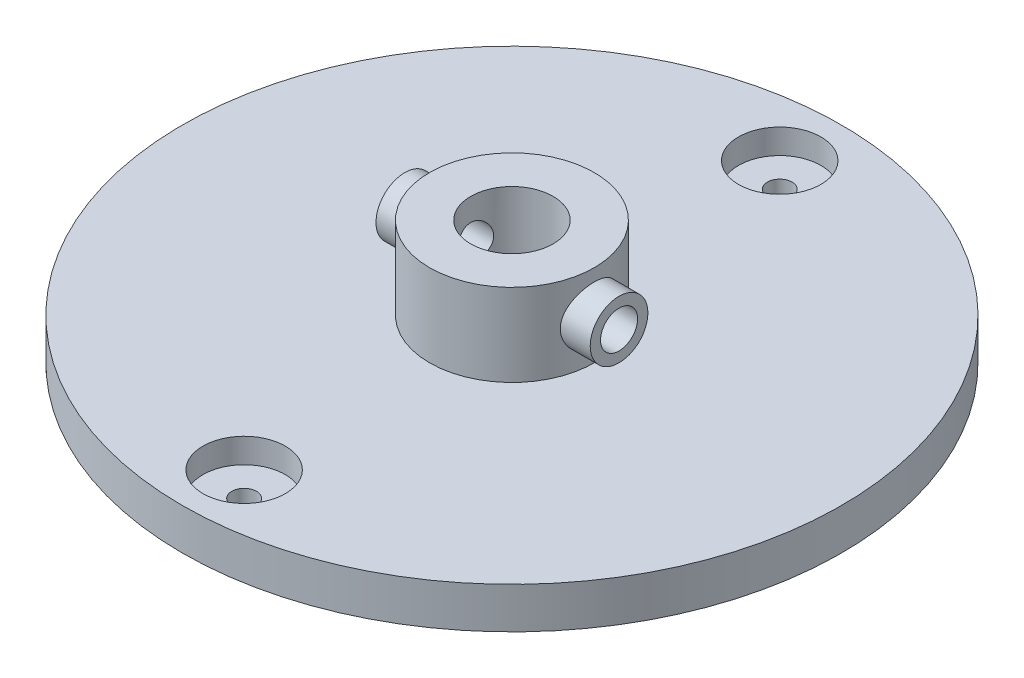
SolidWorks part; units mm, degrees
ref_plane "Front Plane" through (0, 0, 0) normal (0, 0, 1) x (1, 0, 0)
ref_plane "Top Plane" through (0, 0, 0) normal (0, 1, 0) x (1, 0, 0)
ref_plane "Right Plane" through (0, 0, 0) normal (1, 0, 0) x (0, 0, -1)
sketch "Sketch1" plane through (0, 0, 0) normal (0, 1, 0) x (1, 0, 0)
  circle A0 centre (4.1476, -5.4608) radius 40
  dimension "D1" = 80
extrude "Boss-Extrude1" add sketch "Sketch1" along normal blind 5
sketch "Sketch2" plane through (0, 5, 0) normal (0, 1, 0) x (1, 0, 0)
  line L0 (4.1476, -5.4608) -> (44.0651, -2.8922) construction
  line L1 (4.1476, -5.4608) -> (1.5791, 34.4567) construction
  circle A0 centre (4.1476, -5.4608) radius 5
  circle A1 centre (4.1476, -5.4608) radius 40 construction
  dimension "D2" = 10
  dimension "D1" = 40
extrude "Cut-Extrude1" cut sketch "Sketch2" against normal blind 15 contours A0
sketch "Sketch3" plane through (0, 5, 0) normal (0, 1, 0) x (1, 0, 0)
  line L0 (4.1476, -5.4608) -> (4.1476, 13.0674) construction
  line L1 (4.1476, -5.4608) -> (4.1476, -33.9971) construction
  line L2 (4.1476, -5.4608) -> (4.1476, 16.037) construction
  line L3 (4.1476, -5.4608) -> (4.1476, -35.1851) construction
  circle A0 centre (4.1476, -5.4608) radius 32.5 construction
  circle A1 centre (4.1476, 27.0392) radius 5
  circle A3 centre (4.1476, -37.9608) radius 5
  dimension "D1" = 65
  dimension "D3" = 10
  dimension "D2" = 0
extrude "Cut-Extrude2" cut sketch "Sketch3" against normal blind 3
sketch "Sketch5" plane through (0, 2, 0) normal (0, 1, 0) x (1, 0, 0)
  line L0 (4.1476, 27.0392) -> (-12.1024, -33.6066) construction
  line L1 (20.3976, 22.6851) -> (4.1476, -37.9608) construction
  line L2 (4.1476, -37.9608) -> (4.1476, 27.0392) construction
  circle A2 centre (4.1476, -37.9608) radius 1.5
  circle A4 centre (4.1476, 27.0392) radius 1.5
extrude "Cut-Extrude3" cut sketch "Sketch5" against normal blind 33
sketch "Sketch6" plane through (0, 5, 0) normal (0, 1, 0) x (1, 0, 0)
  circle A0 centre (4.1476, -5.4608) radius 10
  circle A1 centre (4.1476, -5.4608) radius 5 construction
  circle A2 centre (4.1476, -5.4608) radius 5
  dimension "D1" = 20
extrude "Boss-Extrude2" add sketch "Sketch6" along normal blind 10
sketch "Sketch7" plane through (0, 0, 0) normal (0, -1, 0) x (-1, 0, 0)
  line L0 (8.9077, -5.4608) -> (-4.1476, -5.4608) construction
  line L1 (-4.1476, -5.4608) -> (-54.4911, -5.4608) construction
  line L2 (0, 8.25) -> (0, -8.25) construction
ref_plane "Plane1" through (4.1476, 0, 5.4608) normal (1, 0, 0) x (0, 0, -1)
sketch "Sketch9" plane through (0, 15, 0) normal (0, 1, 0) x (1, 0, 0)
  line L0 (9.5164, -7.8368) -> (4.1476, -5.4608) construction
  line L1 (4.1476, -5.4608) -> (-24.6408, 7.28) construction
ref_axis "Axis1" through (4.1476, 15, 5.4608) along (0, -1, 0)
sketch "Sketch10" plane through (4.1476, 0, 5.4608) normal (1, 0, 0) x (0, 0, -1)
  line L0 (0, 15) -> (0, 0) construction
  line L1 (5, 15) -> (-5, 15) construction
  circle A0 centre (0, 10) radius 2.25
  dimension "D1" = 4.5
  dimension "D2" = 5
extrude "Cut-Extrude4" cut sketch "Sketch10" against normal mid plane 90
ref_plane "Plane2" through (9.1476, 0, 5.4608) normal (1, 0, 0) x (0, 0, -1)
ref_plane "Plane3" through (-0.8524, 0, 5.4608) normal (1, 0, 0) x (0, 0, -1)
sketch "Sketch11" plane through (9.1476, 0, 5.4608) normal (1, 0, 0) x (0, 0, -1)
  circle A0 centre (0, 10) radius 3.5
  circle A1 centre (0, 10) radius 2.25
  dimension "D1" = 4.5
  dimension "D2" = 7
extrude "Boss-Extrude3" add sketch "Sketch11" along normal blind 8
mirror "Mirror1" about plane through (4.1476, 0, 5.4608) normal (1, 0, 0) of "Boss-Extrude3"
